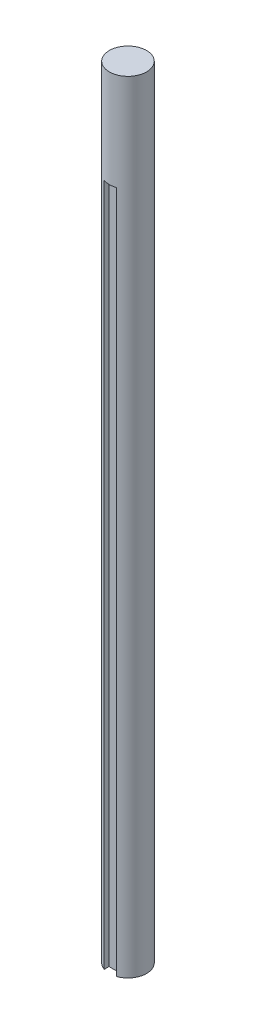
SolidWorks part; units mm, degrees
ref_plane "Front Plane" through (0, 0, 0) normal (0, 0, 1) x (1, 0, 0)
ref_plane "Top Plane" through (0, 0, 0) normal (0, 1, 0) x (1, 0, 0)
ref_plane "Right Plane" through (0, 0, 0) normal (1, 0, 0) x (0, 0, -1)
sketch "Sketch1" plane through (0, 0, 0) normal (0, 1, 0) x (1, 0, 0)
  circle A0 centre (0, 0) radius 4.7625
  dimension "D1" = 9.525
extrude "Boss-Extrude1" add sketch "Sketch1" along normal blind 200
sketch "Sketch2" plane through (0, 0, 0) normal (0, 1, 0) x (1, 0, 0)
  line L0 (-1.6, -3.2625) -> (1.6, -3.2625)
  line L1 (1.6, -3.2625) -> (1.6, -6.7625)
  line L2 (1.6, -6.7625) -> (-1.6, -6.7625)
  line L3 (-1.6, -6.7625) -> (-1.6, -3.2625)
extrude "Cut-Extrude1" cut sketch "Sketch2" against normal mid plane 350
